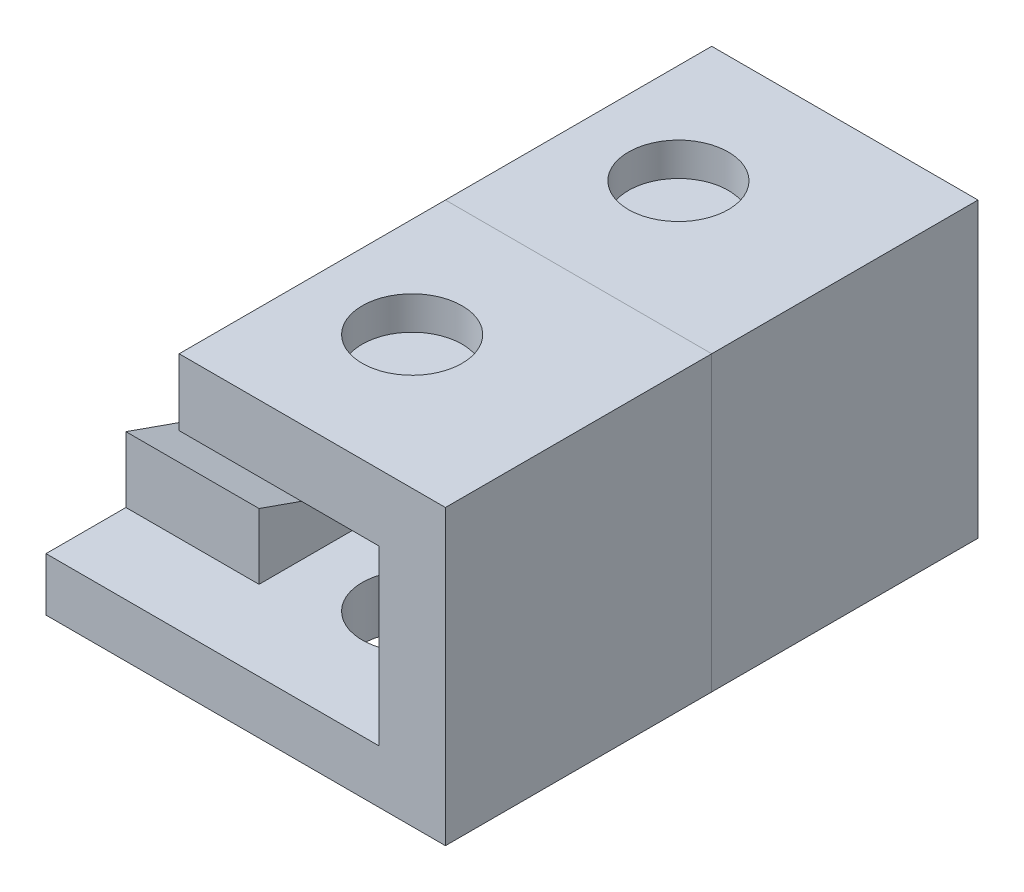
SolidWorks part; units mm, degrees
ref_plane "Front Plane" through (0, 0, 0) normal (0, 0, 1) x (1, 0, 0)
ref_plane "Top Plane" through (0, 0, 0) normal (0, 1, 0) x (1, 0, 0)
ref_plane "Right Plane" through (0, 0, 0) normal (1, 0, 0) x (0, 0, -1)
sketch "Sketch1" plane through (0, 0, 0) normal (0, 1, 0) x (1, 0, 0)
  line L1 (0, 0) -> (31.75, 0)
  line L2 (0, 0) -> (0, 25.4)
  line L3 (0, 25.4) -> (31.75, 25.4)
  line L4 (31.75, 0) -> (31.75, 25.4)
  line L5 (0, 25.4) -> (12.7, 25.4)
  line L6 (0, 25.4) -> (0, 0)
  line L7 (0, 0) -> (12.7, 0)
  line L8 (12.7, 25.4) -> (12.7, 0)
  line L9 (31.75, 25.4) -> (38.1, 25.4)
  line L10 (31.75, 25.4) -> (31.75, 0)
  line L11 (31.75, 0) -> (38.1, 0)
  line L12 (38.1, 25.4) -> (38.1, 0)
  line L13 (0, 25.4) -> (12.7, 25.4)
  line L14 (0, 25.4) -> (0, 17.6554)
  line L15 (0, 17.6554) -> (12.7, 17.6554)
  line L16 (12.7, 25.4) -> (12.7, 17.6554)
  circle A0 centre (22.225, 12.7) radius 4.7625
  dimension "D4" = 6.35
  dimension "D6" = 9.525
  dimension "D1" = 31.75
  dimension "D2" = 25.4
  dimension "D3" = 12.7
  dimension "D5" = 9.525
extrude "Boss-Extrude1" add sketch "Sketch1" along normal blind 2.54 and the other way blind 2.54 contours L3 L8 L1 L4 A0 | L6 L5 L8 L7 region at (13.0175, 0, -8.8277)
extrude "Boss-Extrude2" add sketch "Sketch1<3>" along normal blind 2.54 contours L8 L3 L2 L1 region at (6.35, 0, -8.8277)
sketch "Sketch1<3>" plane through (0, 0, 0) normal (0, 1, 0) x (1, 0, 0) same geometry as "Sketch1"
extrude "Boss-Extrude3" add sketch "Sketch1<4>" along normal blind 25.4 and the other way blind 2.54 contours L12 L9 L4 L11 region at (34.925, 0, -12.7)
sketch "Sketch1<4>" plane through (0, 0, 0) normal (0, 1, 0) x (1, 0, 0) same geometry as "Sketch1"
sketch "Sketch2" plane through (31.75, 0, 0) normal (-1, 0, 0) x (0, 0, 1)
  line L0 (0, 25.4) -> (0, 2.54) construction
  line L1 (-25.4, 25.4) -> (0, 25.4)
  line L2 (-25.4, 25.4) -> (-25.4, 19.05)
  line L3 (-25.4, 19.05) -> (0, 19.05)
  line L4 (0, 25.4) -> (0, 19.05)
  dimension "D1" = 6.35
extrude "Boss-Extrude4" add sketch "Sketch2" along normal blind 19.05
sketch "Sketch4" plane through (0, 25.4, 0) normal (0, 1, 0) x (1, 0, 0)
  line L0 (12.7, 0) -> (12.7, 25.4) construction
  circle A0 centre (22.225, 12.7) radius 4.7625
  circle A1 centre (22.225, 12.7) radius 4.7625 construction
  dimension "D1" = 9.525
  dimension "D2" = 0
extrude "Cut-Extrude1" cut sketch "Sketch4" against normal blind 3.175
sketch "Sketch7" plane through (0, 0, 0) normal (0, 0, 1) x (1, 0, 0)
  line L0 (31.75, 19.05) -> (38.1, 19.05)
  line L1 (38.1, 25.4) -> (38.1, -2.54) construction
sketch "Sketch8" plane through (0, 0, -25.4) normal (0, 0, -1) x (-1, 0, 0)
  line L0 (-31.75, 19.05) -> (-38.1, 19.05)
sketch "Sketch9" plane through (38.1, 0, 0) normal (1, 0, 0) x (0, 0, -1)
  line L0 (0, 19.05) -> (25.4, 19.05)
  line L1 (25.4, 25.4) -> (25.4, -2.54) construction
sketch "Sketch10" plane through (0, 25.4, 0) normal (0, 1, 0) x (1, 0, 0)
  line L0 (38.1, 0) -> (31.75, 0)
  line L1 (12.7, 0) -> (38.1, 0) construction
  line L2 (38.1, 25.4) -> (31.75, 25.4)
  line L3 (12.7, 25.4) -> (38.1, 25.4) construction
  line L4 (31.75, 25.4) -> (31.75, 0)
sketch "Sketch12" plane through (0, 2.54, 0) normal (0, 1, 0) x (1, 0, 0)
  line L0 (12.7, 0) -> (12.7, 25.4) construction
  line L1 (0, 25.4) -> (12.7, 25.4)
  line L2 (0, 25.4) -> (0, 17.7786)
  line L3 (0, 17.7786) -> (12.7, 17.7786)
  line L4 (12.7, 25.4) -> (12.7, 17.7786)
  line L6 (0, 17.7786) -> (12.7, 17.7786)
  line L7 (0, 17.7786) -> (0, 0)
  line L8 (0, 0) -> (12.7, 0)
  line L9 (12.7, 17.7786) -> (12.7, 0)
sketch "Sketch16" plane through (0, 0, 0) normal (-1, 0, 0) x (0, 0, 1)
  line L0 (-17.7786, 2.54) -> (-17.7786, 8.8051)
  line L1 (-25.4, 2.54) -> (-17.7786, 2.54) construction
  line L2 (-17.7786, 2.54) -> (0, 2.54) construction
  line L3 (-17.7786, 8.8051) -> (0, 2.54)
  line L4 (-17.7786, 2.54) -> (0, 2.54)
extrude "Boss-Extrude5" add sketch "Sketch16" against normal blind 12.7
mirror "Mirror3" about plane through (0, -2.54, 0) normal (0, 0, 1) of bodies 108
